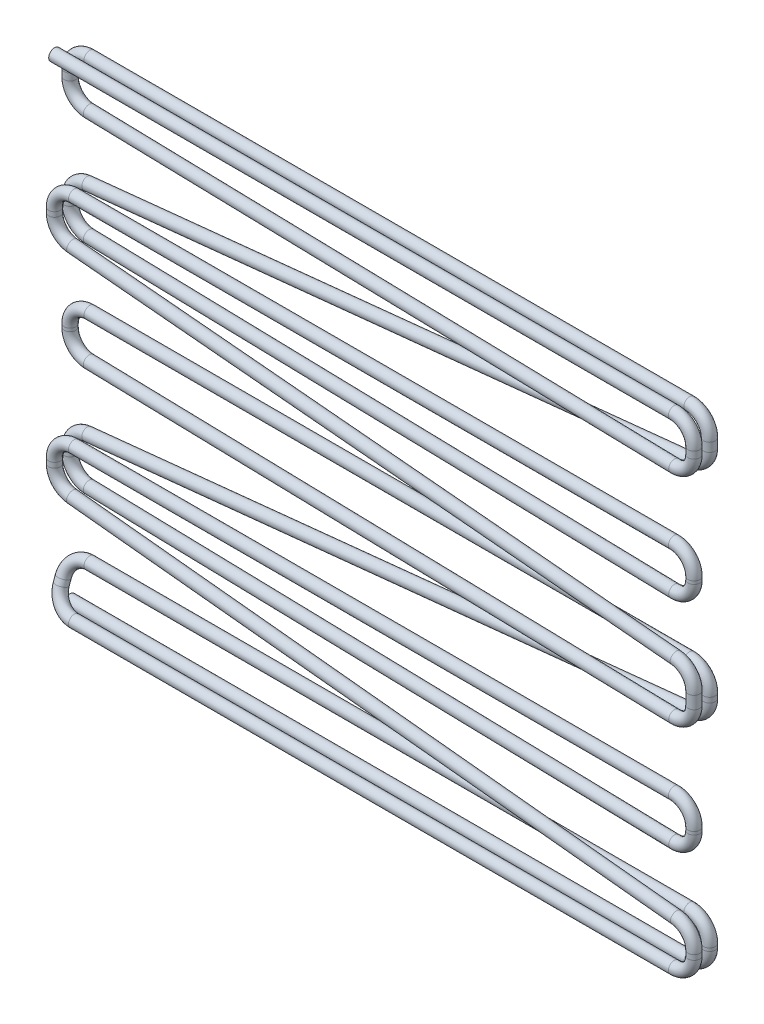
SolidWorks part; units mm, degrees
ref_plane "Front Plane" through (0, 0, 0) normal (0, 0, 1) x (1, 0, 0)
ref_plane "Top Plane" through (0, 0, 0) normal (0, 1, 0) x (1, 0, 0)
ref_plane "Right Plane" through (0, 0, 0) normal (1, 0, 0) x (0, 0, -1)
sketch3d "3DSketch3"
  line L0 (-33, 0, 0) -> (-1.0213, 0, 0)
  line L1 (0, 1.0213, 0) -> (0, 1.1787, 0)
  line L2 (-1.0213, 2.2, 0) -> (-31.9787, 2.2, 0)
  line L3 (-33, 1.2402, 0.349) -> (-33, 0.9598, 0.451)
  line L4 (-31.9787, 0, 0.8) -> (-1.0213, 0, 0.8)
  line L5 (0, 1.0213, 0.8) -> (0, 1.2786, 0.8)
  line L6 (-0.9166, 2.2944, 0.8) -> (-32.0834, 5.5056, 0.8)
  line L7 (-31.9787, 7.8, 0.8) -> (-1.0213, 7.8, 0.8)
  line L8 (0, 6.7787, 0.8) -> (0, 6.6213, 0.8)
  line L9 (0, 12.2213, 0.8) -> (0, 12.8674, 0.8)
  line L10 (-1.021, 5.6, 0.7752) -> (-31.979, 5.6, 0.0248)
  line L11 (-32.0834, 7.8944, 0) -> (-0.9166, 11.1056, 0)
  line L12 (-33, 6.6213, 0) -> (-33, 6.8786, 0)
  line L13 (-33, 6.7787, 0.8) -> (-33, 6.5214, 0.8)
  line L14 (-1.0213, 13.4, 0) -> (-31.9787, 13.4, 0)
  line L15 (-33, 12.2213, 0) -> (-33, 12.3787, 0)
  line L16 (-31.979, 11.2, 0.0248) -> (-1.021, 11.2, 0.7752)
  line L17 (0, 12.3787, 0) -> (0, 12.1214, 0)
  line L18 (-0.9288, 13.8844, 0.8) -> (-32.0712, 16.7156, 0.8)
  line L19 (-1.021, 16.8, 0.7752) -> (-31.979, 16.8, 0.0248)
  line L20 (-33, 17.8213, 0) -> (-33, 18.0786, 0)
  line L21 (-32.0834, 19.0944, 0) -> (-0.9166, 22.3056, 0)
  line L22 (0, 17.8213, 0.8) -> (0, 17.9787, 0.8)
  line L23 (-1.0213, 19, 0.8) -> (-31.9787, 19, 0.8)
  line L24 (-33, 17.9787, 0.8) -> (-33, 17.7326, 0.8)
  line L25 (-31.979, 22.4, 0.0248) -> (-1.021, 22.4, 0.7752)
  line L26 (0, 23.4213, 0.8) -> (0, 23.7787, 0.8)
  line L27 (-1.0213, 24.8, 0.8) -> (-33, 24.8, 0.8)
  line L29 (-33, 23.4213, 0) -> (-33, 23.7787, 0)
  line L30 (-31.9787, 24.8, 0) -> (-1.0213, 24.8, 0)
  line L31 (0, 23.7787, 0) -> (0, 23.3214, 0)
  arc A0 (-31.9787, 24.8, 0) -> (-33, 23.7787, 0) centre (-31.9787, 23.7787, 0) ccw
  arc A1 (-33, 23.4213, 0) -> (-31.979, 22.4, 0.0248) centre (-31.979, 23.4213, 0.0248) ccw
  arc A2 (-31.9787, 19, 0.8) -> (-33, 17.9787, 0.8) centre (-31.9787, 17.9787, 0.8) ccw
  arc A3 (-32.0712, 16.7156, 0.8) -> (-33, 17.7326, 0.8) centre (-31.9787, 17.7326, 0.8) ccw
  arc A4 (-32.0834, 19.0944, 0) -> (-33, 18.0786, 0) centre (-31.9787, 18.0786, 0) ccw
  arc A5 (-33, 17.8213, 0) -> (-31.979, 16.8, 0.0248) centre (-31.979, 17.8213, 0.0248) ccw
  arc A6 (-31.9787, 13.4, 0) -> (-33, 12.3787, 0) centre (-31.9787, 12.3787, 0) ccw
  arc A7 (-33, 12.2213, 0) -> (-31.979, 11.2, 0.0248) centre (-31.979, 12.2213, 0.0248) ccw
  arc A8 (-33, 6.8786, 0) -> (-32.0834, 7.8944, 0) centre (-31.9787, 6.8786, 0) ccw
  arc A9 (-33, 6.6213, 0) -> (-31.979, 5.6, 0.0248) centre (-31.979, 6.6213, 0.0248) ccw
  arc A10 (-31.9787, 7.8, 0.8) -> (-33, 6.7787, 0.8) centre (-31.9787, 6.7787, 0.8) ccw
  arc A11 (-33, 6.5214, 0.8) -> (-32.0834, 5.5056, 0.8) centre (-31.9787, 6.5214, 0.8) ccw
  arc A12 (-31.9787, 2.2, 0) -> (-33, 1.2402, 0.349) centre (-31.9787, 1.2402, 0.349) ccw
  arc A13 (-33, 0.9598, 0.451) -> (-31.9787, 0, 0.8) centre (-31.9787, 0.9598, 0.451) ccw
  arc A14 (-1.0213, 0, 0) -> (0, 1.0213, 0) centre (-1.0213, 1.0213, 0) ccw
  arc A15 (-1.0213, 0, 0.8) -> (0, 1.0213, 0.8) centre (-1.0213, 1.0213, 0.8) ccw
  arc A16 (-1.021, 22.4, 0.7752) -> (0, 23.4213, 0.8) centre (-1.021, 23.4213, 0.7752) ccw
  arc A17 (0, 23.7787, 0.8) -> (-1.0213, 24.8, 0.8) centre (-1.0213, 23.7787, 0.8) ccw
  arc A18 (-1.0213, 24.8, 0) -> (0, 23.7787, 0) centre (-1.0213, 23.7787, 0) ccw
  arc A19 (0, 23.3214, 0) -> (-0.9166, 22.3056, 0) centre (-1.0213, 23.3214, 0) ccw
  arc A20 (0, 17.9787, 0.8) -> (-1.0213, 19, 0.8) centre (-1.0213, 17.9787, 0.8) ccw
  arc A21 (0, 17.8213, 0.8) -> (-1.021, 16.8, 0.7752) centre (-1.021, 17.8213, 0.7752) ccw
  arc A22 (-0.9288, 13.8844, 0.8) -> (0, 12.8674, 0.8) centre (-1.0213, 12.8674, 0.8) ccw
  arc A23 (0, 12.3787, 0) -> (-1.0213, 13.4, 0) centre (-1.0213, 12.3787, 0) ccw
  arc A24 (-1.021, 11.2, 0.7752) -> (0, 12.2213, 0.8) centre (-1.021, 12.2213, 0.7752) ccw
  arc A25 (0, 12.1214, 0) -> (-0.9166, 11.1056, 0) centre (-1.0213, 12.1214, 0) ccw
  arc A26 (-1.0213, 2.2, 0) -> (0, 1.1787, 0) centre (-1.0213, 1.1787, 0) ccw
  arc A27 (0, 1.2786, 0.8) -> (-0.9166, 2.2944, 0.8) centre (-1.0213, 1.2786, 0.8) ccw
  arc A28 (0, 6.7787, 0.8) -> (-1.0213, 7.8, 0.8) centre (-1.0213, 6.7787, 0.8) ccw
  arc A29 (-1.021, 5.6, 0.7752) -> (0, 6.6213, 0.8) centre (-1.021, 6.6213, 0.7752) ccw
  point P0 (0, 0, 0)
  point P1 (-33, 0, 0)
  point P2 (0, 33, 0)
  point P6 (-33, 2.2, 0)
  point P7 (0, 2.2, 0)
  point P10 (0, 2.2, 0.8)
  point P11 (0, 0, 0.8)
  point P12 (-33, 0, 0.8)
  point P13 (-33, 7.8, 0)
  point P14 (-24.8206, -13.6977, 0)
  point P19 (0, 7.8, 0.8)
  point P22 (0, 13.8, 0.8)
  point P26 (-33, 5.6, 0.8)
  point P27 (0, 11.2, 0.8)
  point P31 (-33, 11.2, 0)
  point P32 (-33, 13.4, 0)
  point P33 (0, 13.4, 0)
  point P34 (-33, 24.8, 0)
  point P35 (0, 11.2, 0)
  point P43 (0, 16.8, 0.8)
  point P44 (-33, 16.8, 0)
  point P45 (-33, 16.8, 0.8)
  point P46 (-33, 19, 0)
  point P47 (-33, 19, 0.8)
  point P49 (0, 19, 0.8)
  point P55 (-31.9787, 23.7787, 1.0213)
  point P58 (-33, 22.4, 0)
  point P60 (0, 22.4, 0)
  point P61 (0, 22.4, 0.8)
  point P62 (-33, 24.8, 0)
  point P63 (-33, 24.8, 0.8)
  point P64 (0, 24.8, 0.8)
  point P65 (0, 24.8, 0)
  point P66 (-33, 22.4, 0)
  point P69 (-32.0038, 23.4213, 1.0457)
  point P73 (-33, 19, 0.8)
  point P74 (-31.9787, 17.9787, 1.8213)
  point P77 (-33, 16.8, 0.8)
  point P78 (-31.9787, 17.7326, -0.2213)
  point P81 (-33, 19, 0)
  point P82 (-31.9787, 18.0786, 1.0213)
  point P85 (-33, 16.8, 0)
  point P86 (-32.0038, 17.8213, 1.0457)
  point P89 (-33, 13.4, 0)
  point P90 (-31.9787, 12.3787, 1.0213)
  point P93 (-33, 11.2, 0)
  point P94 (-32.0038, 12.2213, 1.0457)
  point P97 (-33, 7.8, 0)
  point P98 (-31.9787, 6.8786, -1.0213)
  point P101 (-33, 5.6, 0)
  point P102 (-32.0038, 6.6213, 1.0457)
  point P105 (-33, 7.8, 0.8)
  point P106 (-31.9787, 6.7787, 1.8213)
  point P109 (-33, 5.6, 0.8)
  point P110 (-31.9787, 6.5214, 1.8213)
  point P113 (-33, 2.2, 0)
  point P114 (-31.9787, 1.5892, 1.3088)
  point P117 (-33, 0, 0.8)
  point P118 (-31.9787, 1.3088, 1.4108)
  point P121 (0, 0, 0)
  point P122 (-1.0213, 1.0213, 1.0213)
  point P125 (0, 0, 0.8)
  point P126 (-1.0213, 1.0213, 1.8213)
  point P129 (0, 22.4, 0.8)
  point P130 (-1.0457, 23.4213, 1.7962)
  point P133 (0, 24.8, 0.8)
  point P134 (-1.0213, 23.7787, 1.8213)
  point P137 (0, 24.8, 0)
  point P138 (-1.0213, 23.7787, -1.0213)
  point P141 (0, 22.4, 0)
  point P142 (-1.0213, 23.3214, -1.0213)
  point P145 (0, 19, 0.8)
  point P146 (-1.0213, 17.9787, 1.8213)
  point P149 (0, 16.8, 0.8)
  point P150 (-0.9962, 17.8213, -0.2457)
  point P153 (0, 13.8, 0.8)
  point P154 (-1.0213, 12.8674, -0.2213)
  point P157 (0, 13.4, 0)
  point P158 (-1.0213, 12.3787, 1.0213)
  point P161 (0, 11.2, 0.8)
  point P162 (-1.0457, 12.2213, 1.7962)
  point P165 (0, 11.2, 0)
  point P166 (-1.0213, 12.1214, -1.0213)
  point P169 (0, 2.2, 0)
  point P170 (-1.0213, 1.1787, -1.0213)
  point P173 (0, 2.2, 0.8)
  point P174 (-1.0213, 1.2786, 1.8213)
  point P177 (0, 7.8, 0.8)
  point P178 (-1.0213, 6.7787, 1.8213)
  point P181 (0, 5.6, 0.8)
  point P182 (-1.0457, 6.6213, 1.7962)
  dimension "D1" = 1.0213
sketch "Sketch4" plane through (0, 0, 0) normal (1, 0, 0) x (0, 0, -1)
  line L1 (-0.3, -0.3) -> (0.3, -0.3)
  line L2 (-0.3, -0.3) -> (-0.3, 0.3)
  line L3 (-0.3, 0.3) -> (0.3, 0.3)
  line L4 (0.3, -0.3) -> (0.3, 0.3)
  line L5 (-0.3, -0.3) -> (0.3, 0.3) construction
  line L6 (-0.3, 0.3) -> (0.3, -0.3) construction
  point P0 (0, 0)
  dimension "D1" = 0.6
  dimension "D2" = 0.6
ref_plane "Plane1" through (-33, 0, 0) normal (1, 0, 0) x (0, 0, -1)
sketch "Sketch6" plane through (0, 0, 0) normal (0, 0, 1) x (1, 0, 0)
  line L2 (-33.7725, -1.2795) -> (1.4999, -1.2795)
  line L3 (-33.7725, -1.2795) -> (-33.7725, 26.1848)
  line L4 (-33.7725, 26.1848) -> (1.4999, 26.1848)
  line L5 (1.4999, -1.2795) -> (1.4999, 26.1848)
extrude "Boss-Extrude1" [suppressed] add sketch "Sketch6" along normal blind 2.5 and the other way blind 2.5 separate body
sketch "Sketch5" plane through (-33, 0, 0) normal (1, 0, 0) x (0, 0, -1)
  circle A0 centre (0, 0) radius 0.3
sweep "Sweep4" add profiles "Sketch5" path "3DSketch3"
sketch3d "3DSketch4"
  line L0 (-33, 0, 0) -> (-1.0213, 0, 0)
  line L1 (0, 1.0213, 0) -> (0, 1.1787, 0)
  line L2 (-1.0213, 2.2, 0) -> (-31.9787, 2.2, 0)
  line L3 (-33, 1.2402, 0.349) -> (-33, 0.9598, 0.451)
  line L4 (-31.9787, 0, 0.8) -> (-1.0213, 0, 0.8)
  line L5 (0, 1.0213, 0.8) -> (0, 1.2786, 0.8)
  line L6 (-0.9166, 2.2944, 0.8) -> (-32.0834, 5.5056, 0.8)
  line L7 (-31.9787, 7.8, 0.8) -> (-1.0213, 7.8, 0.8)
  line L8 (0, 6.7787, 0.8) -> (0, 6.6213, 0.8)
  line L9 (0, 12.2213, 0.8) -> (0, 12.8674, 0.8)
  line L10 (-1.021, 5.6, 0.7752) -> (-31.979, 5.6, 0.0248)
  line L11 (-32.0834, 7.8944, 0) -> (-0.9166, 11.1056, 0)
  line L12 (-33, 6.6213, 0) -> (-33, 6.8786, 0)
  line L13 (-33, 6.7787, 0.8) -> (-33, 6.5214, 0.8)
  line L14 (-1.0213, 13.4, 0) -> (-31.9787, 13.4, 0)
  line L15 (-33, 12.2213, 0) -> (-33, 12.3787, 0)
  line L16 (-31.979, 11.2, 0.0248) -> (-1.021, 11.2, 0.7752)
  line L17 (0, 12.3787, 0) -> (0, 12.1214, 0)
  line L18 (-0.9288, 13.8844, 0.8) -> (-32.0712, 16.7156, 0.8)
  line L19 (-1.021, 16.8, 0.7752) -> (-31.979, 16.8, 0.0248)
  line L20 (-33, 17.8213, 0) -> (-33, 18.0786, 0)
  line L21 (-32.0834, 19.0944, 0) -> (-0.9166, 22.3056, 0)
  line L22 (0, 17.8213, 0.8) -> (0, 17.9787, 0.8)
  line L23 (-1.0213, 19, 0.8) -> (-31.9787, 19, 0.8)
  line L24 (-33, 17.9787, 0.8) -> (-33, 17.7326, 0.8)
  line L25 (-31.979, 22.4, 0.0248) -> (-1.021, 22.4, 0.7752)
  line L26 (0, 23.4213, 0.8) -> (0, 23.7787, 0.8)
  line L27 (-1.0213, 24.8, 0.8) -> (-33, 24.8, 0.8)
  line L29 (-33, 23.4213, 0) -> (-33, 23.7787, 0)
  line L30 (-31.9787, 24.8, 0) -> (-1.0213, 24.8, 0)
  line L31 (0, 23.7787, 0) -> (0, 23.3214, 0)
  arc A0 (-31.9787, 24.8, 0) -> (-33, 23.7787, 0) centre (-31.9787, 23.7787, 0) ccw
  arc A1 (-33, 23.4213, 0) -> (-31.979, 22.4, 0.0248) centre (-31.979, 23.4213, 0.0248) ccw
  arc A2 (-31.9787, 19, 0.8) -> (-33, 17.9787, 0.8) centre (-31.9787, 17.9787, 0.8) ccw
  arc A3 (-32.0712, 16.7156, 0.8) -> (-33, 17.7326, 0.8) centre (-31.9787, 17.7326, 0.8) ccw
  arc A4 (-32.0834, 19.0944, 0) -> (-33, 18.0786, 0) centre (-31.9787, 18.0786, 0) ccw
  arc A5 (-33, 17.8213, 0) -> (-31.979, 16.8, 0.0248) centre (-31.979, 17.8213, 0.0248) ccw
  arc A6 (-31.9787, 13.4, 0) -> (-33, 12.3787, 0) centre (-31.9787, 12.3787, 0) ccw
  arc A7 (-33, 12.2213, 0) -> (-31.979, 11.2, 0.0248) centre (-31.979, 12.2213, 0.0248) ccw
  arc A8 (-33, 6.8786, 0) -> (-32.0834, 7.8944, 0) centre (-31.9787, 6.8786, 0) ccw
  arc A9 (-33, 6.6213, 0) -> (-31.979, 5.6, 0.0248) centre (-31.979, 6.6213, 0.0248) ccw
  arc A10 (-31.9787, 7.8, 0.8) -> (-33, 6.7787, 0.8) centre (-31.9787, 6.7787, 0.8) ccw
  arc A11 (-33, 6.5214, 0.8) -> (-32.0834, 5.5056, 0.8) centre (-31.9787, 6.5214, 0.8) ccw
  arc A12 (-31.9787, 2.2, 0) -> (-33, 1.2402, 0.349) centre (-31.9787, 1.2402, 0.349) ccw
  arc A13 (-33, 0.9598, 0.451) -> (-31.9787, 0, 0.8) centre (-31.9787, 0.9598, 0.451) ccw
  arc A14 (-1.0213, 0, 0) -> (0, 1.0213, 0) centre (-1.0213, 1.0213, 0) ccw
  arc A15 (-1.0213, 0, 0.8) -> (0, 1.0213, 0.8) centre (-1.0213, 1.0213, 0.8) ccw
  arc A16 (-1.021, 22.4, 0.7752) -> (0, 23.4213, 0.8) centre (-1.021, 23.4213, 0.7752) ccw
  arc A17 (0, 23.7787, 0.8) -> (-1.0213, 24.8, 0.8) centre (-1.0213, 23.7787, 0.8) ccw
  arc A18 (-1.0213, 24.8, 0) -> (0, 23.7787, 0) centre (-1.0213, 23.7787, 0) ccw
  arc A19 (0, 23.3214, 0) -> (-0.9166, 22.3056, 0) centre (-1.0213, 23.3214, 0) ccw
  arc A20 (0, 17.9787, 0.8) -> (-1.0213, 19, 0.8) centre (-1.0213, 17.9787, 0.8) ccw
  arc A21 (0, 17.8213, 0.8) -> (-1.021, 16.8, 0.7752) centre (-1.021, 17.8213, 0.7752) ccw
  arc A22 (-0.9288, 13.8844, 0.8) -> (0, 12.8674, 0.8) centre (-1.0213, 12.8674, 0.8) ccw
  arc A23 (0, 12.3787, 0) -> (-1.0213, 13.4, 0) centre (-1.0213, 12.3787, 0) ccw
  arc A24 (-1.021, 11.2, 0.7752) -> (0, 12.2213, 0.8) centre (-1.021, 12.2213, 0.7752) ccw
  arc A25 (0, 12.1214, 0) -> (-0.9166, 11.1056, 0) centre (-1.0213, 12.1214, 0) ccw
  arc A26 (-1.0213, 2.2, 0) -> (0, 1.1787, 0) centre (-1.0213, 1.1787, 0) ccw
  arc A27 (0, 1.2786, 0.8) -> (-0.9166, 2.2944, 0.8) centre (-1.0213, 1.2786, 0.8) ccw
  arc A28 (0, 6.7787, 0.8) -> (-1.0213, 7.8, 0.8) centre (-1.0213, 6.7787, 0.8) ccw
  arc A29 (-1.021, 5.6, 0.7752) -> (0, 6.6213, 0.8) centre (-1.021, 6.6213, 0.7752) ccw
  point P0 (0, 0, 0)
  point P1 (-33, 0, 0)
  point P2 (0, 33, 0)
  point P6 (-33, 2.2, 0)
  point P7 (0, 2.2, 0)
  point P10 (0, 2.2, 0.8)
  point P11 (0, 0, 0.8)
  point P12 (-33, 0, 0.8)
  point P13 (-33, 7.8, 0)
  point P14 (-24.8206, -13.6977, 0)
  point P19 (0, 7.8, 0.8)
  point P22 (0, 13.8, 0.8)
  point P26 (-33, 5.6, 0.8)
  point P27 (0, 11.2, 0.8)
  point P31 (-33, 11.2, 0)
  point P32 (-33, 13.4, 0)
  point P33 (0, 13.4, 0)
  point P34 (-33, 24.8, 0)
  point P35 (0, 11.2, 0)
  point P43 (0, 16.8, 0.8)
  point P44 (-33, 16.8, 0)
  point P45 (-33, 16.8, 0.8)
  point P46 (-33, 19, 0)
  point P47 (-33, 19, 0.8)
  point P49 (0, 19, 0.8)
  point P55 (-31.9787, 23.7787, 1.0213)
  point P58 (-33, 22.4, 0)
  point P60 (0, 22.4, 0)
  point P61 (0, 22.4, 0.8)
  point P62 (-33, 24.8, 0)
  point P63 (-33, 24.8, 0.8)
  point P64 (0, 24.8, 0.8)
  point P65 (0, 24.8, 0)
  point P66 (-33, 22.4, 0)
  point P69 (-32.0038, 23.4213, 1.0457)
  point P73 (-33, 19, 0.8)
  point P74 (-31.9787, 17.9787, 1.8213)
  point P77 (-33, 16.8, 0.8)
  point P78 (-31.9787, 17.7326, -0.2213)
  point P81 (-33, 19, 0)
  point P82 (-31.9787, 18.0786, 1.0213)
  point P85 (-33, 16.8, 0)
  point P86 (-32.0038, 17.8213, 1.0457)
  point P89 (-33, 13.4, 0)
  point P90 (-31.9787, 12.3787, 1.0213)
  point P93 (-33, 11.2, 0)
  point P94 (-32.0038, 12.2213, 1.0457)
  point P97 (-33, 7.8, 0)
  point P98 (-31.9787, 6.8786, -1.0213)
  point P101 (-33, 5.6, 0)
  point P102 (-32.0038, 6.6213, 1.0457)
  point P105 (-33, 7.8, 0.8)
  point P106 (-31.9787, 6.7787, 1.8213)
  point P109 (-33, 5.6, 0.8)
  point P110 (-31.9787, 6.5214, 1.8213)
  point P113 (-33, 2.2, 0)
  point P114 (-31.9787, 1.5892, 1.3088)
  point P117 (-33, 0, 0.8)
  point P118 (-31.9787, 1.3088, 1.4108)
  point P121 (0, 0, 0)
  point P122 (-1.0213, 1.0213, 1.0213)
  point P125 (0, 0, 0.8)
  point P126 (-1.0213, 1.0213, 1.8213)
  point P129 (0, 22.4, 0.8)
  point P130 (-1.0457, 23.4213, 1.7962)
  point P133 (0, 24.8, 0.8)
  point P134 (-1.0213, 23.7787, 1.8213)
  point P137 (0, 24.8, 0)
  point P138 (-1.0213, 23.7787, -1.0213)
  point P141 (0, 22.4, 0)
  point P142 (-1.0213, 23.3214, -1.0213)
  point P145 (0, 19, 0.8)
  point P146 (-1.0213, 17.9787, 1.8213)
  point P149 (0, 16.8, 0.8)
  point P150 (-0.9962, 17.8213, -0.2457)
  point P153 (0, 13.8, 0.8)
  point P154 (-1.0213, 12.8674, -0.2213)
  point P157 (0, 13.4, 0)
  point P158 (-1.0213, 12.3787, 1.0213)
  point P161 (0, 11.2, 0.8)
  point P162 (-1.0457, 12.2213, 1.7962)
  point P165 (0, 11.2, 0)
  point P166 (-1.0213, 12.1214, -1.0213)
  point P169 (0, 2.2, 0)
  point P170 (-1.0213, 1.1787, -1.0213)
  point P173 (0, 2.2, 0.8)
  point P174 (-1.0213, 1.2786, 1.8213)
  point P177 (0, 7.8, 0.8)
  point P178 (-1.0213, 6.7787, 1.8213)
  point P181 (0, 5.6, 0.8)
  point P182 (-1.0457, 6.6213, 1.7962)
  dimension "D1" = 1.0213
